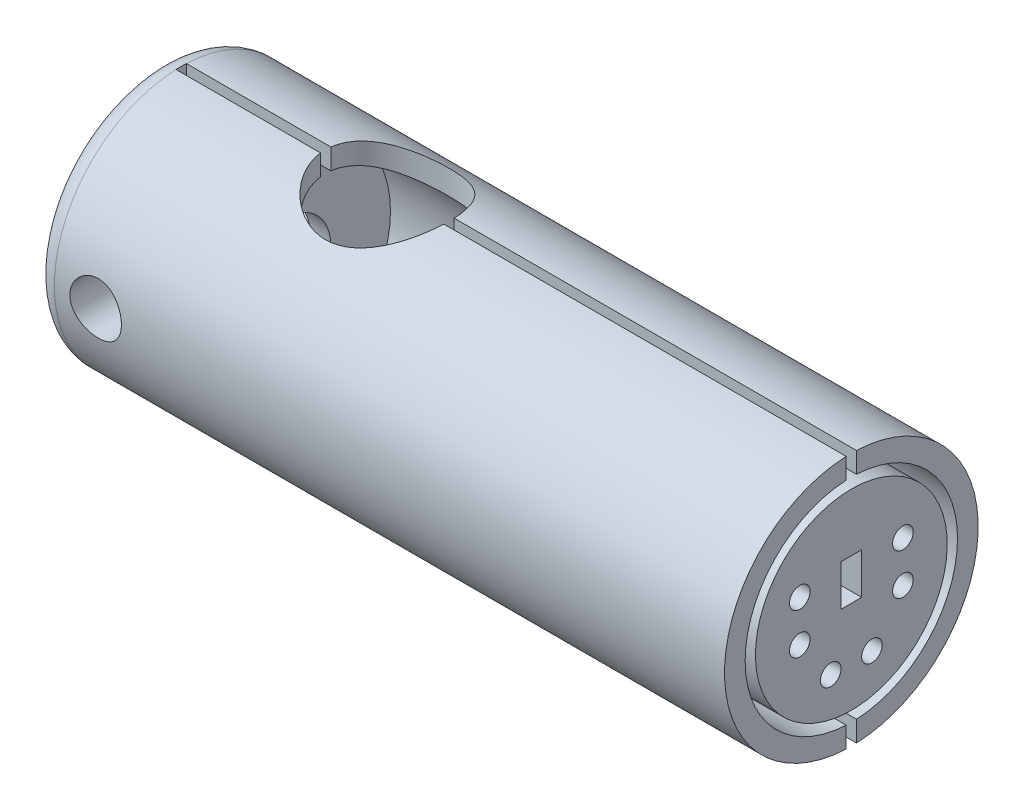
SolidWorks part; units mm, degrees
ref_plane "Спереди" through (0, 0, 0) normal (0, 0, 1) x (1, 0, 0)
ref_plane "Сверху" through (0, 0, 0) normal (0, 1, 0) x (1, 0, 0)
ref_plane "Справа" through (0, 0, 0) normal (1, 0, 0) x (0, 0, -1)
sketch "Эскиз1" plane through (0, 0, 0) normal (0, 0, 1) x (1, 0, 0)
  line L0 (0, 0) -> (0, 6.15)
  line L1 (0, 0) -> (33.5, 0) construction
  line L2 (0, 6.15) -> (33.5, 6.15)
  line L3 (33.5, 0) -> (33.5, 6.15)
  line L4 (0, 0) -> (33.5, 0)
  dimension "D1" = 6.15
  dimension "D2" = 33.5
revolve "Повернуть1" add sketch "Эскиз1" angle 360 about L1
sketch "Эскиз2" plane through (33.5, 0, 0) normal (1, 0, 0) x (0, 0, -1)
  circle A0 centre (0, 0) radius 5.15
  circle A1 centre (0, 0) radius 6.15 construction
  dimension "D1" = 1
extrude "Вырез-Вытянуть1" cut sketch "Эскиз2" against normal blind 27.5
sketch "Эскиз3" plane through (0, 0, 0) normal (-1, 0, 0) x (0, 0, 1)
  circle A0 centre (0, 0) radius 2.25
  dimension "D1" = 4.5
extrude "Вырез-Вытянуть2" cut sketch "Эскиз3" against normal through all
sketch "Эскиз4" plane through (0, 0, 0) normal (-1, 0, 0) x (0, 0, 1)
  line L0 (0, 0) -> (0, 6.15) construction
  line L1 (0, 0) -> (6.15, 0) construction
  circle A0 centre (0, 0) radius 6.15 construction
ref_plane "Плоскость1" through (0, 0, 0) normal (0, 0, 1) x (0, 1, 0)
ref_axis "Ось1" through (6, 0, 0) along (1, 0, 0)
sketch "Эскиз5" plane through (0, 0, 0) normal (0, 0, 1) x (0, 1, 0)
  line L0 (2.25, 0) -> (-2.25, 0) construction
  line L1 (2.25, 0) -> (-2.25, 0) construction
  line L2 (-2.25, -1) -> (-2.25, -5)
  line L3 (-2.25, -1) -> (-3, -1)
  line L4 (-2.25, -5) -> (-3, -5)
  line L5 (-3, -1) -> (-3, -5)
  line L6 (-2.25, -6) -> (2.25, -6) construction
  line L7 (-2.25, -6) -> (2.25, -6) construction
  line L8 (-2.25, 0) -> (-2.25, -6) construction
  dimension "D1" = 1
  dimension "D2" = 1
  dimension "D3" = 0.75
revolve "Вырез-Повернуть1" cut sketch "Эскиз5" angle 360 about axis through (6, 0, 0) along (1, 0, 0)
sketch "Эскиз6" plane through (0, 0, 0) normal (0, 0, 1) x (0, 1, 0)
  line L0 (-3, -1) -> (3, -1) construction
  line L1 (-3, -1) -> (3, -1) construction
  line L2 (3, -5) -> (-3, -5) construction
  line L3 (3, -5) -> (-3, -5) construction
  line L4 (0, -1) -> (0, -5) construction
  circle A0 centre (0, -3) radius 1.25
  dimension "D1" = 2.5
extrude "Вырез-Вытянуть3" cut sketch "Эскиз6" against normal through all and the other way through all
ref_plane "Плоскость2" through (0, 0, 0) normal (0, -1, 0) x (0, 0, 1)
sketch "Эскиз7" plane through (0, 0, 0) normal (0, -1, 0) x (0, 0, 1)
  line L0 (-5.15, -6) -> (5.15, -6) construction
  line L1 (-5.15, -6) -> (5.15, -6) construction
  line L2 (0, -6) -> (0, -11) construction
  circle A0 centre (0, -11) radius 3
  dimension "D1" = 6
  dimension "D2" = 5
extrude "Вырез-Вытянуть4" cut sketch "Эскиз7" against normal through all
fillet "Скругление1" radius 1 1 edges at (0, -6.15, 0)
ref_plane "Плоскость3" through (1, 0, 0) normal (1, 0, 0) x (0, 0, -1)
sketch "Эскиз8" plane through (33.5, 0, 0) normal (1, 0, 0) x (0, 0, -1)
  line L0 (0, 0) -> (0, -6.15) construction
  line L1 (0.25, -6.15) -> (-0.25, -6.15)
  line L2 (0.25, -6.15) -> (0.25, 6.15)
  line L3 (-0.25, -6.15) -> (-0.25, 6.15)
  line L4 (0.25, 6.15) -> (-0.25, 6.15)
  line L5 (0, -6.15) -> (0, 6.15) construction
  circle A0 centre (0, 0) radius 6.15 construction
  dimension "D1" = 0.5
extrude "Вырез-Вытянуть5" cut sketch "Эскиз8" against normal up to surface (32.5 mm away) up to plane "Плоскость3"
sketch "Эскиз9" plane through (33.5, 0, 0) normal (1, 0, 0) x (0, 0, -1)
  line L0 (0, -4.65) -> (0, 4.65) construction
  line L1 (-3.821, -2.65) -> (3.821, -2.65) construction
  line L2 (1, -4.5412) -> (1, 4.5412) construction
  line L3 (2.5, -2.65) -> (2.5, 3.9208) construction
  line L4 (-0.5, 1.85) -> (0.5, 1.85)
  line L5 (-0.5, 1.85) -> (-0.5, -0.15)
  line L6 (0.5, 1.85) -> (0.5, -0.15)
  line L7 (-0.5, -0.15) -> (0.5, -0.15)
  circle A0 centre (0, 0) radius 4.65
  arc A1 (-0.25, 5.1439) -> (-0.25, -5.1439) centre (0, 0) ccw construction
  circle A2 centre (1, -2.65) radius 0.5
  circle A3 centre (2.5, -0.65) radius 0.5
  circle A4 centre (2.5, 1.35) radius 0.5
  circle A5 centre (-2.5, 1.35) radius 0.5
  circle A6 centre (-2.5, -0.65) radius 0.5
  circle A7 centre (-1, -2.65) radius 0.5
  arc A8 (0.25, -5.1439) -> (0.25, 5.1439) centre (0, 0) ccw construction
  circle A9 centre (0, 0) radius 5.15 construction
  point P26 (0, 1.85)
  dimension "D1" = 0.5
  dimension "D4" = 1
  dimension "D6" = 2
  dimension "D2" = 2
  dimension "D3" = 1
  dimension "D5" = 2
  dimension "D7" = 1.5
  dimension "D8" = 1
  dimension "D9" = 2
  dimension "D10" = 2.5
extrude "Бобышка-Вытянуть1" add sketch "Эскиз9" against normal blind 12 separate body
sketch "Эскиз10" plane through (0, 0, 0) normal (0, 0, 1) x (0, 1, 0)
  line L0 (-4.65, -33.5) -> (4.65, -33.5) construction
  line L1 (-4.65, -33.5) -> (4.65, -33.5) construction
  line L2 (4.65, -21.5) -> (-4.65, -21.5) construction
  line L3 (4.65, -21.5) -> (-4.65, -21.5)
  line L4 (0, -33.5) -> (0, -21.5) construction
  circle A0 centre (0, -27.5) radius 1.5
  dimension "D1" = 3
extrude "Бобышка-Вытянуть2" add sketch "Эскиз10" along normal up to surface and the other way up to surface contours A0 region at (27.5, 0, 0) up to face at (1.7771, 0.2588, 6.1446) other way up to face at (1.7771, -0.2588, -6.1446)
sketch "Эскиз11" plane through (33.5, 0, 0) normal (1, 0, 0) x (0, 0, -1)
  arc A0 (0.25, -6.1449) -> (0.25, 6.1449) centre (0, 0) ccw construction
  circle A1 centre (0, 0) radius 6.15
